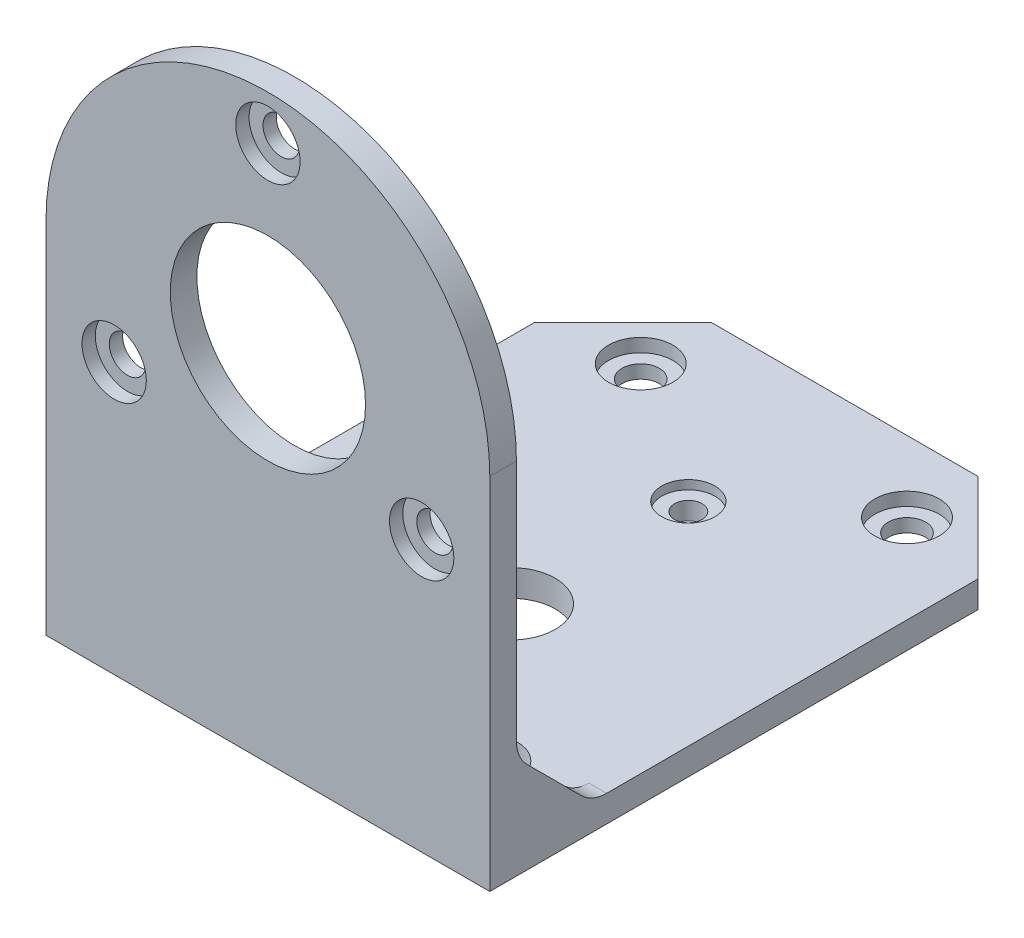
SolidWorks part; units mm, degrees
material "Nylon 101"
ref_plane "前视基准面" through (0, 0, 0) normal (0, 0, 1) x (1, 0, 0)
ref_plane "上视基准面" through (0, 0, 0) normal (0, 1, 0) x (1, 0, 0)
ref_plane "右视基准面" through (0, 0, 0) normal (1, 0, 0) x (0, 0, -1)
sketch "草图1" plane through (0, 0, 0) normal (0, 0, 1) x (1, 0, 0)
  line L0 (0, 0) -> (0, 90) construction
  circle A0 centre (0, 90) radius 11
  arc A2 (19, 72) -> (20, 75) centre (24, 72) cw
  circle A3 centre (0, 90) radius 25
  arc A5 (-19, 72) -> (-20, 75) centre (-24, 72) ccw
  circle A6 centre (0, 110) radius 2.05
  circle A7 centre (17.3205, 80) radius 2.05
  circle A8 centre (-17.3205, 80) radius 2.05
  point P30 (0, 90)
  dimension "D4" = 50
  dimension "D8" = 4.1
  dimension "D2" = 22
  dimension "D10" = 20
  dimension "D12" = 5
  dimension "D9" = 40
  dimension "D11" = 3
extrude "凸台-拉伸1" add sketch "草图1" along normal mid plane 3 contours A3 | L0 A3 A5 | L0 A2 A3 | L0 | L0 region at (23.0463, 82.3179, 0)
sketch "草图3" plane through (0, 0, -1.5) normal (0, 0, -1) x (-1, 0, 0)
  line L0 (-25, 90) -> (-25, 52.5)
  line L1 (-25, 52.5) -> (25, 52.5)
  line L2 (25, 52.5) -> (25, 90)
  circle A0 centre (0, 90) radius 25 construction
  circle A1 centre (0, 90) radius 25 construction
  circle A2 centre (0, 90) radius 25
  circle M5 centre (0, 90) radius 25
  dimension "D1" = 37.5
extrude "凸台-拉伸2" add sketch "草图3" against normal up to surface (3 mm away) contours L0 L1 M5 | L1 L2 M5 region at (0, 62.3039, -1.5) up to face at (11, 90, 1.5)
sketch "草图4" plane through (0, 0, 1.5) normal (0, 0, 1) x (1, 0, 0)
  line L0 (25, 52.5) -> (25, 49.5)
  line L1 (25, 49.5) -> (-25, 49.5)
  line L2 (-25, 52.5) -> (-25, 49.5)
  line L3 (25, 52.5) -> (-25, 52.5) construction
  line L4 (25, 52.5) -> (-25, 52.5)
  dimension "D1" = 3
extrude "凸台-拉伸3" add sketch "草图4" against normal blind 65
sketch "草图6" plane through (0, 52.5, 0) normal (0, 1, 0) x (1, 0, 0)
  line L0 (-15, 63.5) -> (-25, 53.5)
  line L1 (25, 53.5) -> (15, 63.5)
  line L4 (-25, 1.5) -> (25, 1.5)
  line L5 (25, 1.5) -> (25, 63.5)
  line L6 (25, 63.5) -> (-25, 63.5)
  line L7 (-25, 63.5) -> (-25, 1.5)
  line L8 (-25, 1.5) -> (25, 1.5)
  line L9 (25, 1.5) -> (25, 53.5)
  line L10 (15, 63.5) -> (-15, 63.5)
  line L11 (-25, 53.5) -> (-25, 1.5)
  line M8 (25, 1.5) -> (25, 63.5)
  line M9 (25, 63.5) -> (-25, 63.5)
  line M10 (-25, 63.5) -> (-25, 1.5)
  dimension "D1" = 0
extrude "切除-拉伸1" cut sketch "草图6" against normal blind 55 contours L0 M9 M10 | L1 M8 M9 region at (-21.6667, 52.5, -60.1667) region at (21.6667, 52.5, -60.1667)
sketch "草图7" plane through (0, 52.5, 0) normal (0, 1, 0) x (1, 0, 0)
  line L0 (0, 0) -> (0, 63.5) construction
  line L1 (15, 63.5) -> (-15, 63.5) construction
  line L2 (-25, 53.5) -> (-25, 1.5) construction
  line L3 (-15, 55.5) -> (15, 55.5) construction
  line L4 (-15, 55.5) -> (-15, 8) construction
  line L5 (-15, 8) -> (15, 8) construction
  line L6 (15, 55.5) -> (15, 8) construction
  line L7 (-15, 55.5) -> (15, 8) construction
  line L8 (-15, 8) -> (15, 55.5) construction
  circle A0 centre (-15, 55.5) radius 2.1
  circle A1 centre (15, 55.5) radius 2.1
  circle A2 centre (15, 8) radius 2.1
  circle A3 centre (-15, 8) radius 2.1
  point P5 (0, 31.75)
  dimension "D3" = 4.2
  dimension "D4" = 4.2
  dimension "D5" = 4.2
  dimension "D6" = 4.2
  dimension "D1" = 8
  dimension "D2" = 10
  dimension "D7" = 47.5
  dimension "D8" = 30
extrude "切除-拉伸2" cut sketch "草图7" against normal blind 55
sketch "草图9" plane through (0, 52.5, 0) normal (0, 1, 0) x (1, 0, 0)
  circle A0 centre (-15, 55.5) radius 3.625
  circle A1 centre (15, 55.5) radius 3.625
  circle A2 centre (15, 8) radius 3.625
  circle A3 centre (-15, 8) radius 3.625
  dimension "D1" = 7.25
  dimension "D2" = 7.25
  dimension "D3" = 7.25
  dimension "D4" = 7.25
extrude "切除-拉伸3" cut sketch "草图9" against normal blind 1.5
sketch "草图10" plane through (0, 52.5, 0) normal (0, 1, 0) x (1, 0, 0)
  line L0 (-25, 24.75) -> (25, 24.75) construction
  line L1 (-25, 53.5) -> (-25, 1.5) construction
  line L2 (25, 53.5) -> (25, 1.5) construction
  line L3 (25, 1.5) -> (-25, 1.5) construction
  line L4 (0, 24.75) -> (0, 50.696) construction
  dimension "D1" = 23.25
sketch "草图11" plane through (0, 0, 1.5) normal (0, 0, 1) x (1, 0, 0)
  circle A0 centre (0, 110) radius 2.05 construction
  circle A1 centre (0, 110) radius 2.05
  circle A2 centre (-17.3205, 80) radius 2.05 construction
  circle A3 centre (-17.3205, 80) radius 2.05
  circle A4 centre (17.3205, 80) radius 2.05 construction
  circle A5 centre (17.3205, 80) radius 2.05
  circle A6 centre (0, 110) radius 3.625
  circle A7 centre (17.3205, 80) radius 3.625
  circle A8 centre (-17.3205, 80) radius 3.625
  dimension "D1" = 7.25
  dimension "D2" = 7.25
  dimension "D3" = 7.25
extrude "切除-拉伸4" cut sketch "草图11" against normal blind 1.5
sketch "草图12" plane through (0, 49.5, 0) normal (0, -1, 0) x (1, 0, 0)
  circle A0 centre (1.115, -4.7515) radius 1.55 construction
  circle A1 centre (1.115, -4.7515) radius 1.55
  circle A2 centre (1.115, -44.7515) radius 1.55 construction
  circle A3 centre (1.115, -44.7515) radius 1.55
  circle A4 centre (1.115, -24.7515) radius 5 construction
  circle A5 centre (1.115, -24.7515) radius 5
extrude "切除-拉伸5" cut sketch "草图12" against normal blind 6.5
sketch "草图13" plane through (0, 52.5, 0) normal (0, 1, 0) x (1, 0, 0)
  circle A0 centre (1.115, 44.7515) radius 3
  circle A1 centre (1.115, 4.7515) radius 3
  circle M1 centre (1.115, 4.7515) radius 1.55
  circle M2 centre (1.115, 44.7515) radius 1.55
  dimension "D1" = 6
  dimension "D2" = 6
extrude "切除-拉伸13" cut sketch "草图13" against normal offset from surface (1 mm away) 2 contours A1 M1 | A0 M2 region at (-1.8002, 52.5, -44.7515) region at (-1.8002, 52.5, -4.7515) up to face at (2.665, 49.5, -4.7515)
sketch "草图14" plane through (25, 0, 0) normal (1, 0, 0) x (0, 0, -1)
  line L0 (1.5, 61) -> (10, 52.5)
  line L2 (53.5, 52.5) -> (1.5, 52.5) construction
  line L4 (1.5, 52.5) -> (10, 52.5)
  line L5 (1.5, 90) -> (1.5, 52.5) construction
  line L6 (1.5, 52.5) -> (1.5, 61)
  dimension "D1" = 8.5
  dimension "D2" = 45
extrude "凸台-拉伸4" add sketch "草图14" against normal blind 2
fillet "圆角1" radius 4 2 edges at (24, 52.5, -10) (24, 61, -1.5)
mirror "镜向1" about plane through (0, 0, 0) normal (1, 0, 0) of "圆角1", "凸台-拉伸4"
